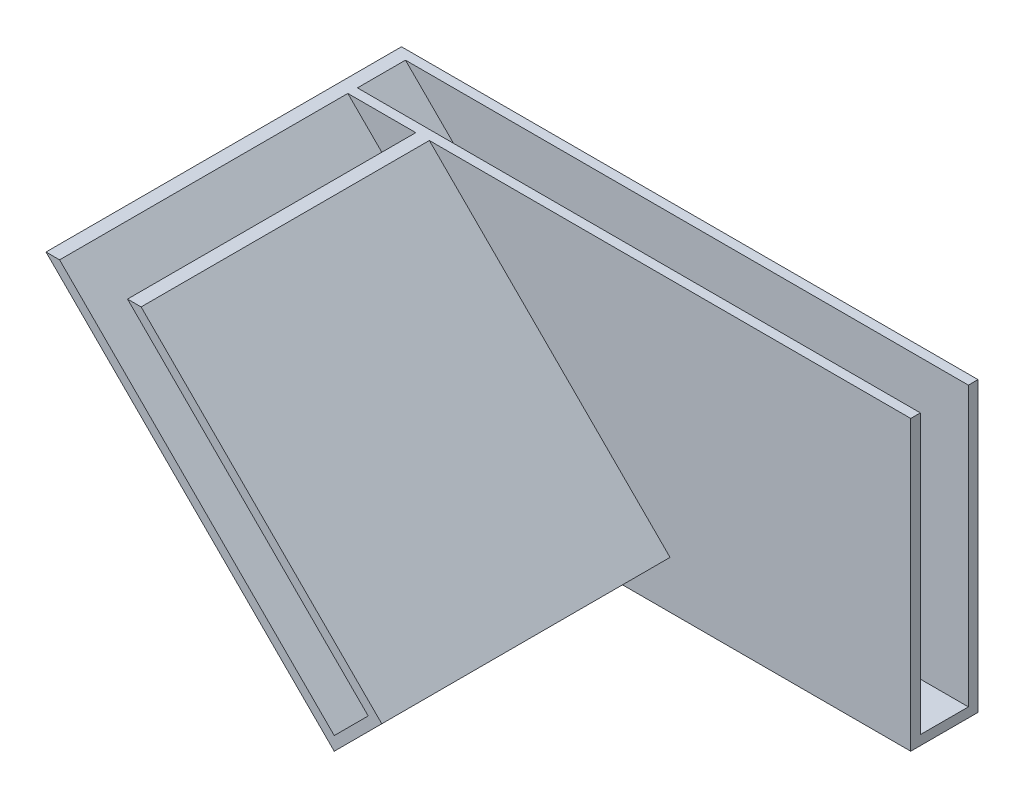
SolidWorks part; units mm, degrees
ref_plane "Front Plane" through (0, 0, 0) normal (0, 0, 1) x (1, 0, 0)
ref_plane "Top Plane" through (0, 0, 0) normal (0, 1, 0) x (1, 0, 0)
ref_plane "Right Plane" through (0, 0, 0) normal (1, 0, 0) x (0, 0, -1)
sketch "Sketch1" plane through (0, 0, 0) normal (0, 0, 1) x (1, 0, 0)
  line L1 (0, 0) -> (30, 0)
  line L2 (0, 0) -> (0, 30)
  line L3 (0, 30) -> (30, 30)
  line L4 (30, 0) -> (30, 30)
  dimension "D1" = 30
  dimension "D2" = 30
extrude "Boss-Extrude1" add sketch "Sketch1" along normal blind 7
sketch "Sketch2" plane through (0, 0, 0) normal (-1, 0, 0) x (0, 0, 1)
  line L4 (0, 30) -> (0, 0)
  line L5 (0, 0) -> (7, 0)
  line L6 (7, 0) -> (7, 30)
  line L7 (7, 30) -> (0, 30)
  line L8 (0, 30) -> (0, 0)
  line L9 (0, 0) -> (7, 0)
  line L10 (7, 0) -> (7, 30)
  line L11 (7, 30) -> (0, 30)
  dimension "D1" = 0
extrude "Boss-Extrude2" add sketch "Sketch2" along normal blind 30
sketch "Sketch3" plane through (0, 0, 7) normal (0, 0, 1) x (1, 0, 0)
  line L0 (-30, 30) -> (0, 0)
  line L1 (0, 0) -> (-30, 0)
  line L2 (-30, 0) -> (-30, 30)
extrude "Cut-Extrude1" cut sketch "Sketch3" against normal blind 30
shell "Shell1" thickness 1 removed face at (0, 30, 3.5) removed face at (30, 15, 3.5)
sketch "Sketch6" plane through (0, 0, 7) normal (0, 0, 1) x (1, 0, 0)
  line L0 (0, 0) -> (4.9497, 4.9497)
  line L1 (4.9497, 4.9497) -> (-20.1005, 30)
  line L2 (30, 30) -> (-30, 30) construction
  line L3 (-20.1005, 30) -> (-30, 30)
  line L4 (-30, 30) -> (0, 0)
  dimension "D1" = 7
extrude "Boss-Extrude3" add sketch "Sketch6" along normal blind 30
sketch "Sketch9" plane through (0, 0, 0) normal (0, 0, -1) x (-1, 0, 0)
  line L4 (0, 0) -> (30, 30)
  line L5 (30, 30) -> (-30, 30)
  line L6 (-30, 30) -> (-30, 0)
  line L7 (-30, 0) -> (0, 0)
  line L8 (0, 0) -> (30, 30)
  line L9 (30, 30) -> (-30, 30)
  line L10 (-30, 30) -> (-30, 0)
  line L11 (-30, 0) -> (0, 0)
  dimension "D1" = 0
shell "Shell2" thickness 1 removed face at (-11.2877, 16.2374, 37) removed face at (-3.7373, 30, 10.2)
